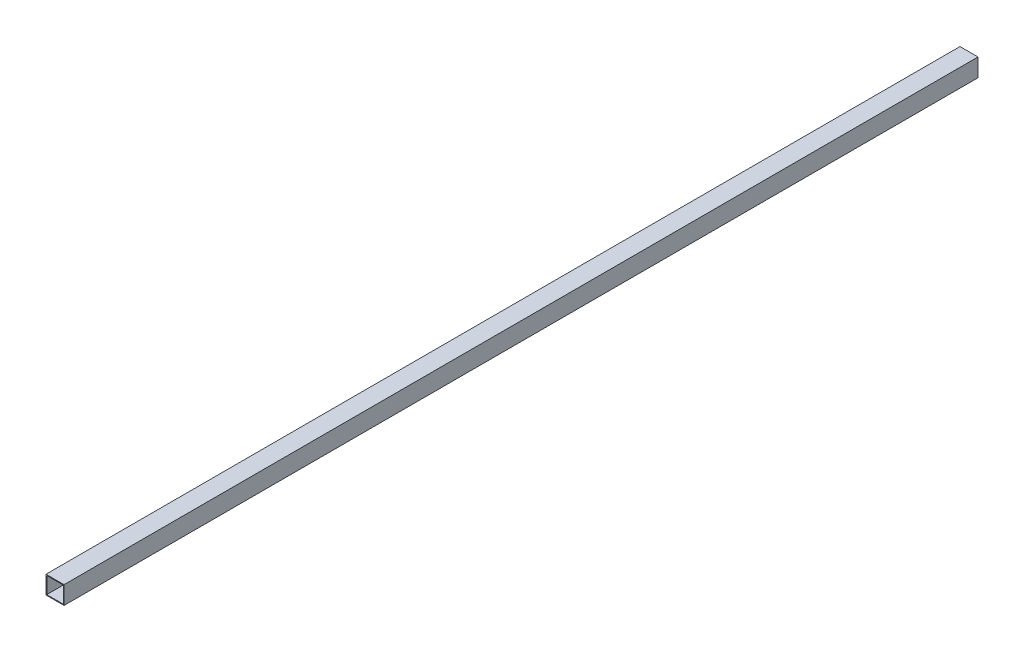
SolidWorks part; units mm, degrees
material "Plain Carbon Steel"
ref_plane "Front Plane" through (0, 0, 0) normal (0, 0, 1) x (1, 0, 0)
ref_plane "Top Plane" through (0, 0, 0) normal (0, 1, 0) x (1, 0, 0)
ref_plane "Right Plane" through (0, 0, 0) normal (1, 0, 0) x (0, 0, -1)
sketch "Sketch2" plane through (0, 0, 0) normal (0, 0, 1) x (1, 0, 0)
  line L0 (0, 19.05) -> (1.5875, 19.05) construction
  line L1 (0, 0) -> (38.1, 0)
  line L2 (0, 0) -> (0, 38.1)
  line L3 (0, 38.1) -> (38.1, 38.1)
  line L4 (38.1, 0) -> (38.1, 38.1)
  line L5 (1.5875, 1.5875) -> (36.5125, 1.5875)
  line L6 (1.5875, 1.5875) -> (1.5875, 36.5125)
  line L7 (1.5875, 36.5125) -> (36.5125, 36.5125)
  line L8 (36.5125, 1.5875) -> (36.5125, 36.5125)
  line L9 (19.05, 36.5125) -> (19.05, 38.1) construction
  line L10 (36.5125, 19.05) -> (38.1, 19.05) construction
  line L11 (19.05, 0) -> (19.05, 1.5875) construction
  dimension "D1" = 38.1
  dimension "D2" = 1.5875
  dimension "D3" = 38.1
extrude "Boss-Extrude1" add sketch "Sketch2" along normal blind 1930.4
